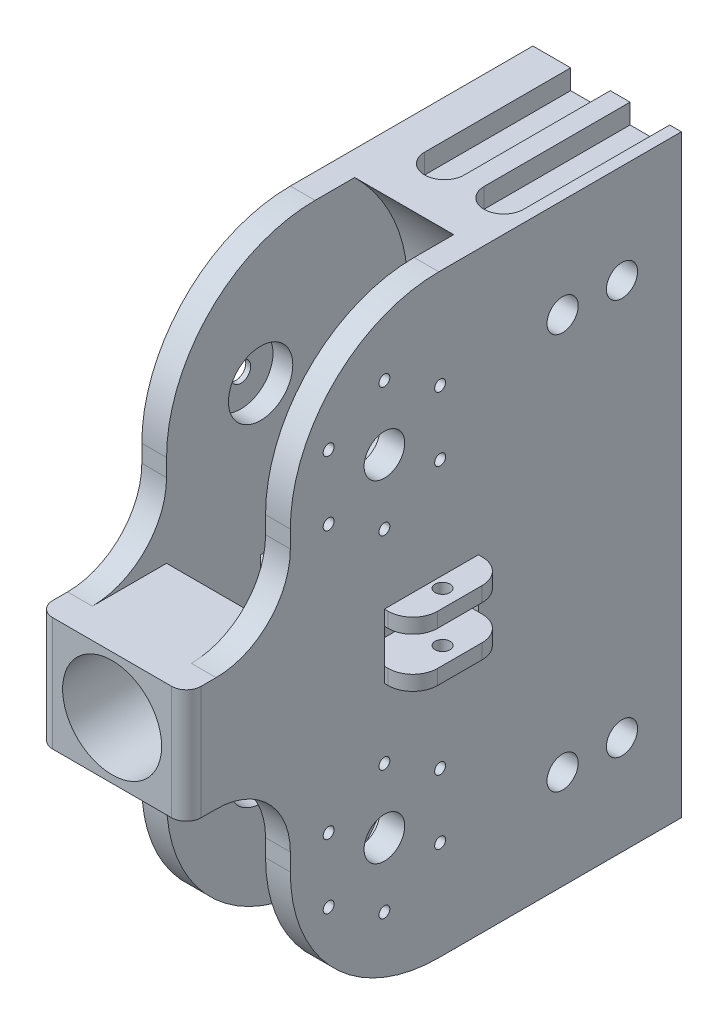
SolidWorks part; units mm, degrees
ref_plane "前视基准面" through (0, 0, 0) normal (0, 0, 1) x (1, 0, 0)
ref_plane "上视基准面" through (0, 0, 0) normal (0, 1, 0) x (1, 0, 0)
ref_plane "右视基准面" through (0, 0, 0) normal (1, 0, 0) x (0, 0, -1)
sketch "草图1" plane through (0, 0, 0) normal (0, 0, 1) x (1, 0, 0)
  line L1 (15, -11.5) -> (-15, -11.5)
  line L2 (15, -11.5) -> (15, 11.5)
  line L3 (15, 11.5) -> (-15, 11.5)
  line L4 (-15, -11.5) -> (-15, 11.5)
  line L5 (15, -11.5) -> (-15, 11.5) construction
  line L6 (15, 11.5) -> (-15, -11.5) construction
  circle A0 centre (0, 0) radius 9
  dimension "D1" = 18
  dimension "D2" = 30
  dimension "D3" = 23
extrude "凸台-拉伸1" add sketch "草图1" along normal blind 50
sketch "草图2" plane through (0, 0, 50) normal (0, 0, 1) x (1, 0, 0)
  line L1 (-15, 11.5) -> (15, 11.5)
  line L2 (-15, 11.5) -> (-15, -11.5)
  line L3 (-15, -11.5) -> (15, -11.5)
  line L4 (15, 11.5) -> (15, -11.5)
  circle A0 centre (0, 0) radius 9
  dimension "D1" = 18
  dimension "D2" = 15
  dimension "D3" = 11.5
extrude "凸台-拉伸2" add sketch "草图2" along normal blind 70
sketch "草图3" plane through (0, -11.5, 0) normal (0, -1, 0) x (1, 0, 0)
  line L0 (10, 95) -> (-10, 95)
  line L1 (-10, 95) -> (-10, 65)
  line L2 (-10, 65) -> (10, 65)
  line L3 (10, 65) -> (10, 95)
  line L4 (10, 80) -> (-10, 80) construction
  line L6 (15, 120) -> (15, 0) construction
  line L7 (-15, 120) -> (15, 120) construction
  point P7 (0, 95)
  dimension "D1" = 20
  dimension "D2" = 30
  dimension "D3" = 15
  dimension "D4" = 25
extrude "切除-拉伸1" cut sketch "草图3" against normal through all
fillet "圆角1" radius 2.4 1 edges at (9, 0, 95)
fillet "圆角2" radius 1 1 edges at (-9, 0, 65)
chamfer "倒角1" distance 4 angle 45 2 edges at (0, -11.5, 65) (0, 11.5, 65)
chamfer "倒角2" distance 4 angle 45 2 edges at (0, -11.5, 95) (0, 11.5, 95)
sketch "草图9" plane through (-15, 0, 0) normal (-1, 0, 0) x (0, 0, 1)
  line L0 (61, -3.5) -> (61, 3.5)
  line L2 (20, -55) -> (20, 55) construction
  line L3 (61, 3.5) -> (80, 3.5)
  line L4 (80, 3.5) -> (80, -3.5)
  line L5 (80, -3.5) -> (61, -3.5)
  line L6 (120, -11.5) -> (0, -11.5) construction
  line L7 (120, 11.5) -> (0, 11.5) construction
  dimension "D1" = 8
  dimension "D2" = 8
  dimension "D3" = 19
  dimension "D4" = 41
sketch "草图15" plane through (0, 0, 0) normal (0, 0, -1) x (-1, 0, 0)
  line L1 (-15, 11.5) -> (15, 11.5)
  line L2 (-15, 11.5) -> (-15, -11.5)
  line L3 (-15, -11.5) -> (15, -11.5)
  line L4 (15, 11.5) -> (15, -11.5)
extrude "切除-拉伸5" cut sketch "草图15" against normal blind 20
extrude "切除-拉伸6" cut sketch "草图9" against normal up to surface (30 mm away) up to face at (15, 0, 70)
sketch "草图23" plane through (-15, 0, 0) normal (-1, 0, 0) x (0, 0, 1)
  line L1 (61, 3.5) -> (80, 3.5)
  line L2 (61, 3.5) -> (61, 6.5)
  line L3 (61, 6.5) -> (80, 6.5)
  line L4 (80, 3.5) -> (80, 6.5)
  line L5 (61, -3.5) -> (80, -3.5)
  line L6 (61, -3.5) -> (61, -6.5)
  line L7 (61, -6.5) -> (80, -6.5)
  line L8 (80, -3.5) -> (80, -6.5)
  dimension "D1" = 19
  dimension "D2" = 3
  dimension "D3" = 3
  dimension "D4" = 19
extrude "凸台-拉伸7" add sketch "草图23" along normal blind 5.75
sketch "草图24" plane through (0, 3.5, 0) normal (0, -1, 0) x (1, 0, 0)
  line L0 (-20.75, 61) -> (-20.75, 80) construction
  line L1 (-20.75, 80) -> (-15, 80) construction
  circle A0 centre (-17.25, 70.5) radius 1.5
  dimension "D1" = 3
  dimension "D2" = 3.5
  dimension "D3" = 9.5
extrude "切除-拉伸7" cut sketch "草图24" against normal through all both and the other way through all
sketch "草图25" plane through (15, 0, 0) normal (1, 0, 0) x (0, 0, -1)
  line L0 (-61, 3.5) -> (-80, 3.5) construction
  line L1 (-61, -3.5) -> (-80, -3.5)
  line L2 (-61, -3.5) -> (-61, -6.5)
  line L3 (-61, -6.5) -> (-80, -6.5)
  line L4 (-80, -3.5) -> (-80, -6.5)
  line L5 (-61, 3.5) -> (-80, 3.5)
  line L6 (-61, 3.5) -> (-61, 6.5)
  line L7 (-61, 6.5) -> (-80, 6.5)
  line L8 (-80, 3.5) -> (-80, 6.5)
  line L9 (-61, -3.5) -> (-61, 3.5) construction
  dimension "D1" = 19
  dimension "D2" = 3
  dimension "D3" = 19
  dimension "D4" = 3
extrude "凸台-拉伸8" add sketch "草图25" along normal blind 5.75
sketch "草图26" plane through (0, -3.5, 0) normal (0, 1, 0) x (1, 0, 0)
  line L0 (20.75, -61) -> (15, -61) construction
  line L1 (20.75, -61) -> (20.75, -80) construction
  circle A0 centre (17.25, -70.5) radius 1.5
  dimension "D1" = 3
  dimension "D2" = 9.5
  dimension "D3" = 3.5
extrude "切除-拉伸8" cut sketch "草图26" against normal through all both and the other way through all
fillet "圆角7" radius 5 8 edges at (-20.75, -5, 61) (-20.75, -5, 80) (-20.75, 5, 80) (-20.75, 5, 61) (20.75, 5, 80) (20.75, 5, 61) (20.75, -5, 61) (20.75, -5, 80)
sketch "草图27" plane through (0, 11.5, 0) normal (0, 1, 0) x (1, 0, 0)
  line L2 (15, -20) -> (15, -99)
  line L3 (15, -99) -> (10, -99)
  line L4 (10, -61) -> (10, -99)
  line L6 (-10, -61) -> (-10, -99)
  line L7 (-10, -99) -> (-15, -99)
  line L8 (-15, -20) -> (-15, -99)
  line L9 (-15, -120) -> (-15, -20) construction
  line L10 (10, -61) -> (-10, -61)
  line L12 (15, -20) -> (-15, -20)
extrude "凸台-拉伸9" add sketch "草图27" along normal blind 48.5
sketch "草图28" plane through (0, -11.5, 0) normal (0, -1, 0) x (1, 0, 0)
  line L0 (10, 99) -> (15, 99)
  line L1 (15, 120) -> (15, 20) construction
  line L2 (15, 99) -> (15, 20)
  line L3 (15, 20) -> (-15, 20)
  line L4 (-15, 20) -> (-15, 99)
  line L5 (-15, 99) -> (-10, 99)
  line L6 (-10, 99) -> (-10, 61)
  line L7 (-10, 61) -> (10, 61)
  line L8 (10, 61) -> (10, 99)
extrude "凸台-拉伸10" add sketch "草图28" along normal blind 48.5
sketch "草图29" plane through (15, 0, 0) normal (1, 0, 0) x (0, 0, -1)
  line L0 (-80, 33.5) -> (-80, -33.5) construction
  line L1 (-80, 3.5) -> (-80, -3.5) construction
  circle A0 centre (-80, 33.5) radius 4.1
  circle A1 centre (-80, -33.5) radius 4.1
  point P4 (-80, 0)
  dimension "D2" = 8.2
  dimension "D3" = 8.2
  dimension "D1" = 67
extrude "切除-拉伸9" cut sketch "草图29" against normal up to next
sketch "草图30" plane through (-10, 0, 0) normal (1, 0, 0) x (0, 0, -1)
  circle A0 centre (-80, -33.5) radius 6.5
  circle A1 centre (-80, 33.5) radius 6.5
  dimension "D1" = 13
  dimension "D2" = 13
extrude "切除-拉伸10" cut sketch "草图30" against normal blind 4
sketch "草图31" plane through (-14, 0, 0) normal (1, 0, 0) x (0, 0, -1)
  circle A0 centre (-80, 33.5) radius 2
  circle A1 centre (-80, -33.5) radius 2
  dimension "D1" = 4
  dimension "D2" = 4
extrude "切除-拉伸11" cut sketch "草图31" against normal through all
fillet "圆角8" radius 30 4 edges at (-12.5, -60, 99) (12.5, -60, 99) (-12.5, 60, 99) (12.5, 60, 99)
sketch "草图33" plane through (10, 0, 0) normal (-1, 0, 0) x (0, 0, 1)
  line L2 (61, 60) -> (46.75, 45.75) construction
  line L3 (46.75, 45.75) -> (46.75, 25.75) construction
  line L4 (46.75, 25.75) -> (61, 11.5) construction
  line L9 (61, -11.5) -> (46.75, -25.75) construction
  line L10 (46.75, -25.75) -> (46.75, -45.75) construction
  line L11 (46.75, -45.75) -> (61, -60) construction
  line L17 (61, 60) -> (61, 11.5)
  line L18 (61, -11.5) -> (61, -60)
  spline S0 degree 3 poles (61, 60) (46.75, 45.75) (46.75, 25.75) (61, 11.5) knots 0 0 0 0 1 1 1 1
  spline S1 degree 3 poles (61, -11.5) (46.75, -25.75) (46.75, -45.75) (61, -60) knots 0 0 0 0 1 1 1 1
  dimension "D1" = 20
  dimension "D2" = 20
  dimension "D3" = 45
  dimension "D4" = 45
  dimension "D5" = 45
  dimension "D6" = 45
extrude "切除-拉伸12" cut sketch "草图33" along normal blind 20
fillet "圆角9" radius 15 4 edges at (12.5, 11.5, 99) (-12.5, -11.5, 99) (12.5, -11.5, 99) (-12.5, 11.5, 99)
fillet "圆角10" radius 3 2 edges at (-15, 0, 120) (15, 0, 120)
sketch "草图34" plane through (15, 0, 0) normal (1, 0, 0) x (0, 0, -1)
  line L0 (-69, 60) -> (-20, 60) construction
  line L1 (-20, 60) -> (-20, -60) construction
  line L2 (-44, 40) -> (-44, -40) construction
  circle A0 centre (-32, -40) radius 3.15
  circle A1 centre (-44, -40) radius 3.15
  circle A2 centre (-32, 40) radius 3.15
  circle A3 centre (-44, 40) radius 3.15
  point P8 (-44, 0)
  dimension "D1" = 6.3
  dimension "D2" = 6.3
  dimension "D3" = 6.3
  dimension "D4" = 6.3
  dimension "D5" = 20
  dimension "D6" = 12
  dimension "D7" = 12
  dimension "D8" = 60
extrude "切除-拉伸13" cut sketch "草图34" against normal through all
sketch "草图35" plane through (0, 60, 0) normal (0, 1, 0) x (1, 0, 0)
  line L0 (8.6317, -13.5) -> (8.6317, -49.5) construction
  line L1 (12.6317, -13.5) -> (12.6317, -49.5)
  line L2 (4.6317, -13.5) -> (4.6317, -49.5)
  line L3 (-3.3683, -13.5) -> (-3.3683, -49.5) construction
  line L4 (0.6317, -13.5) -> (0.6317, -49.5)
  line L5 (-7.3683, -13.5) -> (-7.3683, -49.5)
  arc A0 (12.6317, -13.5) -> (4.6317, -13.5) centre (8.6317, -13.5) ccw
  arc A1 (4.6317, -49.5) -> (12.6317, -49.5) centre (8.6317, -49.5) ccw
  arc A2 (0.6317, -13.5) -> (-7.3683, -13.5) centre (-3.3683, -13.5) ccw
  arc A3 (-7.3683, -49.5) -> (0.6317, -49.5) centre (-3.3683, -49.5) ccw
  point P2 (8.6317, -31.5)
  point P7 (-3.3683, -31.5)
  dimension "D1" = 4
  dimension "D2" = 4
  dimension "D3" = 36
  dimension "D4" = 36
extrude "切除-拉伸14" cut sketch "草图35" against normal blind 4
mirror "镜向1" about plane through (0, 0, 0) normal (0, 1, 0) of "切除-拉伸14"
sketch "草图36" plane through (15, 0, 0) normal (1, 0, 0) x (0, 0, -1)
  line L0 (16.5, 0) -> (-16.5, 0) construction
  circle A0 centre (-80, -33.5) radius 13 construction
  circle A1 centre (-80, -46.5) radius 1.1
  circle A2 centre (-91.2583, -40) radius 1.1
  circle A3 centre (-91.2583, -27) radius 1.1
  circle A4 centre (-80, -20.5) radius 1.1
  circle A5 centre (-68.7417, -27) radius 1.1
  circle A6 centre (-68.7417, -40) radius 1.1
  circle A7 centre (-68.7417, 40) radius 1.1
  circle A8 centre (-68.7417, 27) radius 1.1
  circle A9 centre (-80, 20.5) radius 1.1
  circle A10 centre (-91.2583, 27) radius 1.1
  circle A11 centre (-91.2583, 40) radius 1.1
  circle A12 centre (-80, 46.5) radius 1.1
  point P17 (-80, -33.5)
  point P30 (-80, 33.5)
  dimension "D1" = 26
  dimension "D2" = 2.2
  dimension "D3" = 6
extrude "切除-拉伸15" cut sketch "草图36" against normal blind 10
sketch "草图37" plane through (0, 0, 120) normal (0, 0, 1) x (1, 0, 0)
  circle A0 centre (0, 0) radius 10
  dimension "D1" = 20
extrude "切除-拉伸16" cut sketch "草图37" against normal blind 27
